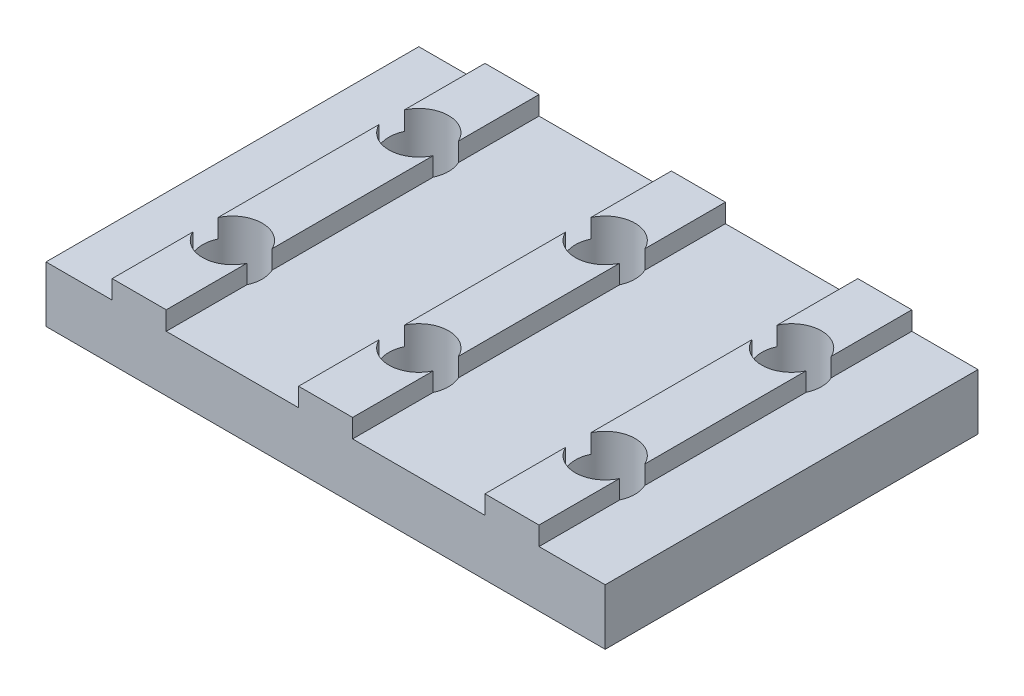
SolidWorks part; units mm, degrees
ref_plane "Front Plane" through (0, 0, 0) normal (0, 0, 1) x (1, 0, 0)
ref_plane "Top Plane" through (0, 0, 0) normal (0, 1, 0) x (1, 0, 0)
ref_plane "Right Plane" through (0, 0, 0) normal (1, 0, 0) x (0, 0, -1)
sketch "Esquisse1" plane through (0, 0, 0) normal (0, 0, 1) x (1, 0, 0)
  line L0 (-5, 0) -> (-5, 3)
  line L1 (-5, 3) -> (-1.45, 3)
  line L2 (-1.45, 3) -> (-1.45, 4)
  line L3 (-1.45, 4) -> (1.45, 4)
  line L4 (1.45, 4) -> (1.45, 3)
  line L5 (1.45, 3) -> (5, 3)
  line L6 (5, 3) -> (5, 0)
  line L7 (5, 0) -> (-5, 0)
  point P11 (0, 0)
  dimension "D1" = 10
  dimension "D2" = 3
  dimension "D3" = 1
  dimension "D4" = 2.9
  dimension "D5" = 3.55
extrude "Main" add sketch "Esquisse1" along normal blind 20
sketch "Esquisse2" plane through (0, 4, 0) normal (0, 1, 0) x (1, 0, 0)
  line L0 (0, -2.2) -> (0, 2.2) construction
  line L1 (-1.45, 0) -> (-5, 0) construction
  line L2 (-1.45, -20) -> (-5, -20) construction
  circle A0 centre (0, -5) radius 1.6
  circle A1 centre (0, -15) radius 1.6
  dimension "D2" = 5
  dimension "D3" = 3.2
  dimension "D1" = 5
extrude "TopHole" cut sketch "Esquisse2" against normal through all
ref_axis "Axe1" through (-5.5, 0, 0) along (1, 0, 0)
pattern_linear "Répétition linéaire1" count 3 spacing 10 along (-1, 0, 0) of "TopHole", "Main"
